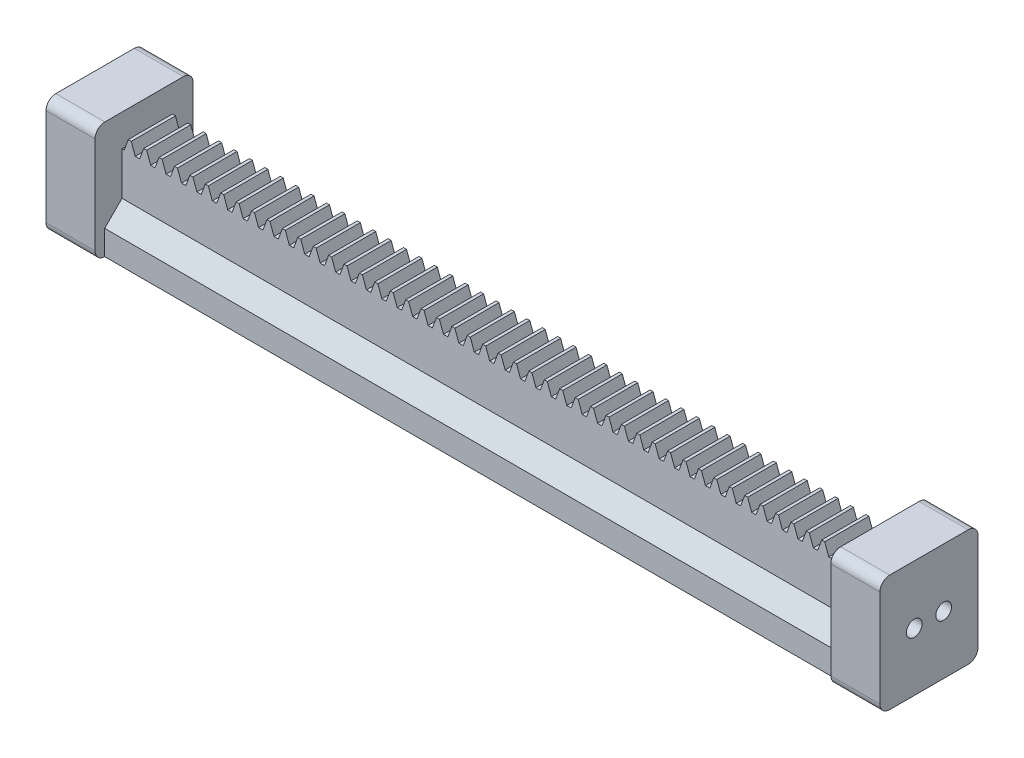
SolidWorks part; units mm, degrees
extrude "Blank" add sketch "BlankSke" against normal blind 9
sketch "BlankSke" plane through (0, 0, 0) normal (0, 0, 1) x (1, 0, 0)
  line L1 (0, 0) -> (150, 0)
  line L2 (0, 0) -> (0, 11)
  line L3 (0, 11) -> (150, 11)
  line L4 (150, 0) -> (150, 11)
  dimension "Length" = 150
ref_plane "Plane1" through (0, 0, 0) normal (0, 0, 1) x (1, 0, 0)
ref_plane "Plane2" through (0, 0, 0) normal (0, 1, 0) x (1, 0, 0)
ref_plane "Plane3" through (0, 0, 0) normal (1, 0, 0) x (0, 0, -1)
other "Configuration Table"
sketch "HoldingSke" plane through (0, 0, 0) normal (0, 1, 0) x (1, 0, 0)
  line L0 (0, 0) -> (0.1392, 0.9903)
  line L1 (-15, 0) -> (100, 0) construction
  line L2 (0, 0) -> (-2.1039, 2.3779)
  line L3 (0, 0) -> (-11.863, 4.5341)
  line L4 (0, 0) -> (5.6657, 6.5177)
  line L5 (0, 0) -> (-23.7986, -8.8762)
  line L6 (0, 0) -> (-10.5278, -7.1032)
  line L9 (-71.009, 38.7566) -> (69.9449, 90.0596)
  line L10 (-76.2, 3.3779) -> (-66.2, 3.3779)
  line L11 (0, 0) -> (-9, 0)
  line L12 (-76.2, 101.6) -> (-76.162, 101.6)
  line L13 (24.9733, 27.94) -> (52.9518, 28.4284)
  line L14 (24.9733, 27.94) -> (24.9743, 27.94)
  line L15 (24.9733, 27.94) -> (100.4006, 29.5858)
  circle A0 centre (0, 0) radius 19.05
  circle A1 centre (0, 0) radius 5
  circle A2 centre (0, 0) radius 12.7
  dimension "Num_teeth" = 49
  dimension "Width" = 9
  dimension "Length" = 150
  dimension "Pitch_height" = 10
sketch "TooCutSkeIll" plane through (0, 0, 0) normal (0, 0, 1) x (1, 0, 0)
  line L0 (-1.2538, 10.9737) -> (-0.5045, 8.9152)
  line L1 (-0.2687, 8.75) -> (0.2687, 8.75)
  line L2 (0.5045, 8.9152) -> (1.2538, 10.9737)
  line L3 (150, 11) -> (0, 11) construction
  line L4 (0, 0) -> (0, 64.897) construction
  line L5 (-13.208, 10) -> (12.954, 10) construction
  line L6 (0, 0) -> (150, 0) construction
  line L7 (0.8994, 10) -> (0.8994, 48.7463) construction
  line L8 (-0.8994, 10) -> (-0.8994, 48.7463) construction
  line L9 (1.2914, 11) -> (1.2914, 11.0254)
  line L10 (-1.2914, 11) -> (-1.2914, 11.0254)
  line L11 (-1.2914, 11.0254) -> (1.2914, 11.0254)
  arc A0 (0.2687, 8.75) -> (0.5045, 8.9152) centre (0.2687, 9.001) ccw
  arc A1 (-0.5045, 8.9152) -> (-0.2687, 8.75) centre (-0.2687, 9.001) ccw
  arc A2 (1.2914, 11) -> (1.2538, 10.9737) centre (1.2914, 10.96) ccw
  arc A3 (-1.2538, 10.9737) -> (-1.2914, 11) centre (-1.2914, 10.96) ccw
  dimension "Addendum_plus" = 1.0254
  dimension "Pitch_height" = 10
  dimension "Pressure_angle" = 20
  dimension "Gap_width" = 1.7988
  dimension "Dedendum" = 1.25
extrude "ToothCutIll" [suppressed] cut sketch "TooCutSkeIll" against normal through all
sketch "TooCutSkeSim" plane through (0, 0, 0) normal (0, 0, 1) x (1, 0, 0)
  line L0 (0.4444, 8.75) -> (-0.4444, 8.75)
  line L1 (1.2726, 11.0254) -> (0.4444, 8.75)
  line L2 (0, 17.4625) -> (0, 53.467) construction
  line L3 (1.2726, 11.0254) -> (-1.2726, 11.0254)
  line L6 (-1.2726, 11.0254) -> (-0.4444, 8.75)
  line L9 (-0.8994, 10) -> (0.8994, 10) construction
  line L10 (0, 0) -> (150, 0) construction
  line L11 (0.8994, 10) -> (0.8994, 53.467) construction
  line L12 (-0.8994, 10) -> (-0.8994, 53.467) construction
  dimension "Addendum_plus" = 1.0254
  dimension "Pitch_height" = 10
  dimension "Pressure_angle" = 20
  dimension "Gap_width" = 1.7988
  dimension "Dedendum" = 1.25
extrude "ToothCutSim" cut sketch "TooCutSkeSim" against normal through all
pattern_linear "TeethCuts" count 49 spacing 3.1416 along (1, 0, 0) of "ToothCutIll", "ToothCutSim"
ref_plane "Simetría" through (75, 0, 0) normal (1, 0, 0) x (0, 0, -1)
sketch "Sketch4" plane through (150, 0, 0) normal (1, 0, 0) x (0, 0, -1)
  line L0 (0, 0) -> (-3.5355, -3.5355)
  line L1 (0, 0) -> (0, 9.7171) construction
  line L2 (-3.5355, -3.5355) -> (-3.5355, -8.5355)
  line L3 (4.5, 11) -> (4.5, 0) construction
  line L4 (9, 11) -> (0, 11) construction
  line L5 (9, 0) -> (0, 0) construction
  line L6 (12.5355, -3.5355) -> (12.5355, -8.5355)
  line L7 (9, 0) -> (12.5355, -3.5355)
  line L8 (12.5355, -8.5355) -> (-3.5355, -8.5355)
  line L9 (9, 0) -> (0, 0)
  dimension "D1" = 5
  dimension "D2" = 45
  dimension "D3" = 5
extrude "Boss-Extrude4" add sketch "Sketch4" against normal through all
sketch "Sketch5" plane through (150, 0, 0) normal (1, 0, 0) x (0, 0, -1)
  line L0 (12.5, -8.5355) -> (-3.5, -8.5355)
  line L1 (12.5355, -8.5355) -> (-3.5355, -8.5355) construction
  line L2 (12.5355, -8.5355) -> (12.5355, 11) construction
  line L3 (12.5355, 11) -> (-3.5355, 11) construction
  line L4 (-3.5355, -8.5355) -> (-3.5355, 11) construction
  line L6 (-5.5, -6.5355) -> (-5.5, 13.2322)
  line L7 (-3.5, 15.2322) -> (12.5, 15.2322)
  line L8 (14.5, -6.5355) -> (14.5, 13.2322)
  line L9 (-5.5, -12.7678) -> (14.5, 15.2322) construction
  line L10 (-5.5, 15.2322) -> (14.5, -12.7678) construction
  arc A0 (-3.5, 15.2322) -> (-5.5, 13.2322) centre (-3.5, 13.2322) ccw
  arc A1 (12.5, 15.2322) -> (14.5, 13.2322) centre (12.5, 13.2322) cw
  arc A2 (14.5, -6.5355) -> (12.5, -8.5355) centre (12.5, -6.5355) cw
  arc A3 (-3.5, -8.5355) -> (-5.5, -6.5355) centre (-3.5, -6.5355) cw
  point P4 (4.5, 1.2322)
  dimension "D3" = 2
  dimension "D1" = 28
  dimension "D2" = 20
extrude "Boss-Extrude5" add sketch "Sketch5" along normal blind 10
mirror "Mirror2" about plane through (75, 0, 0) normal (1, 0, 0) of "Boss-Extrude5"
sketch "Sketch6" plane through (160, 0, 0) normal (1, 0, 0) x (0, 0, -1)
  line L0 (1.5, 3.3483) -> (7.5, 3.3483) construction
  circle A0 centre (1.5, 3.3483) radius 1.6
  circle A1 centre (7.5, 3.3483) radius 1.6
  point P3 (4.5, 3.3483)
  dimension "D1" = 3.2
  dimension "D2" = 3.2
  dimension "D3" = 3
extrude "Cut-Extrude1" cut sketch "Sketch6" against normal up to surface (10 mm away) up to face at (150, 2.7983, -4.5)
equation "' \"Module@HoldingSke\" = 6.35"
equation "' \"Num_teeth@HoldingSke\" = 12"
equation "' \"Ap@HoldingSke\" =  20"
equation "' \"Ap@HoldingSke\" = 20"
equation "' \"Width@HoldingSke\" = 0.25 * 25.4"
equation "' \"Show_teeth@HoldingSke\" = 500"
equation "' \"Backlash@HoldingSke\" = 0.009 * 25.4"
equation "' \"Addendum_fac@HoldingSke\" = 1.0"
equation "' \"Dedendum_fac@HoldingSke\" = 1.25"
equation "' \"Dedendum_add@HoldingSke\" = 0.00005 * 25.4"
equation "' \"Clearance_fac@HoldingSke\" = 0.25"
equation "' \"Pitch_height@HoldingSke\" = 1 * 25.4"
equation "' \"Length@HoldingSke\" = 4.71 * 25.4"
equation "\"Pitch@HoldingSke\" = 1 / \"Module@HoldingSke\""
equation "\"MPH@HoldingSke\" = \"Dedendum_fac@HoldingSke\" / \"Pitch@HoldingSke\" + 2 * \"Dedendum_add@HoldingSke\" + 0.002 * 25.4"
equation "\"MPH@HoldingSke\" = ((sgn( \"MPH@HoldingSke\" - \"Pitch_height@HoldingSke\")+1)*( \"MPH@HoldingSke\" - \"Pitch_height@HoldingSke\"))/2 + \"Pitch_height@HoldingSke\""
equation "\"Blank_height@BlankSke\" = \"Pitch_height@HoldingSke\" + \"Addendum_fac@HoldingSke\"  / \"Pitch@HoldingSke\" "
equation "\"Length@BlankSke\" =  \"Length@HoldingSke\""
equation "\"Pressure_angle@TooCutSkeIll\" = \"Ap@HoldingSke\""
equation "\"Addendum_plus@TooCutSkeIll\" =  \"Addendum_fac@HoldingSke\"  / \"Pitch@HoldingSke\" + 0.001 *25.4"
equation "\"Dedendum@TooCutSkeIll\" = \"Dedendum_fac@HoldingSke\"  / \"Pitch@HoldingSke\""
equation "\"Pitch_height@TooCutSkeIll\" =  \"MPH@HoldingSke\""
equation "\"Gap_width@TooCutSkeIll\" = 3.14159265 / 2 / \"Pitch@HoldingSke\" + 6 * \"Backlash@HoldingSke\""
equation "\"Pressure_angle@TooCutSkeSim\" = \"Ap@HoldingSke\""
equation "\"Addendum_plus@TooCutSkeSim\" =  \"Addendum_fac@HoldingSke\"  / \"Pitch@HoldingSke\" + 0.001 * 25.4"
equation "\"Dedendum@TooCutSkeSim\" = \"Dedendum_fac@HoldingSke\"  / \"Pitch@HoldingSke\""
equation "\"Pitch_height@TooCutSkeSim\" =  \"MPH@HoldingSke\""
equation "\"Gap_width@TooCutSkeSim\" = 3.14159265 / 2 / \"Pitch@HoldingSke\" + 6 * \"Backlash@HoldingSke\""
equation "\"Root_fillet@TooCutSkeIll\" = \"Clearance_fac@HoldingSke\" / \"Pitch@HoldingSke\" + \"Dedendum_add@HoldingSke\""
equation "\"Break_rad@TooCutSkeIll\" = 0.02 / \"Pitch@HoldingSke\" * 2"
equation "\"Linear_pitch@TeethCuts\" = 3.14159265 / \"Pitch@HoldingSke\""
equation "\"Num_teeth@HoldingSke\" = int( ( \"Length@HoldingSke\" + 0 ) / (3.14159265 / \"Pitch@HoldingSke\")) + 0.9999  + 1"
equation " \"Num_teeth@TeethCuts\" = int( \"Show_teeth@HoldingSke\" ) + 1"
equation " \"Num_teeth@TeethCuts\" = ((sgn( \"Num_teeth@TeethCuts\" - \"Num_teeth@HoldingSke\" )-1)*( \"Num_teeth@TeethCuts\" - \"Num_teeth@HoldingSke\" ))/-2+ \"Num_teeth@HoldingSke\""
equation " \"Num_teeth@TeethCuts\" = ((sgn( \"Num_teeth@TeethCuts\" - 2.0)+1)*( \"Num_teeth@TeethCuts\" - 2.0))/2 +2.0"
